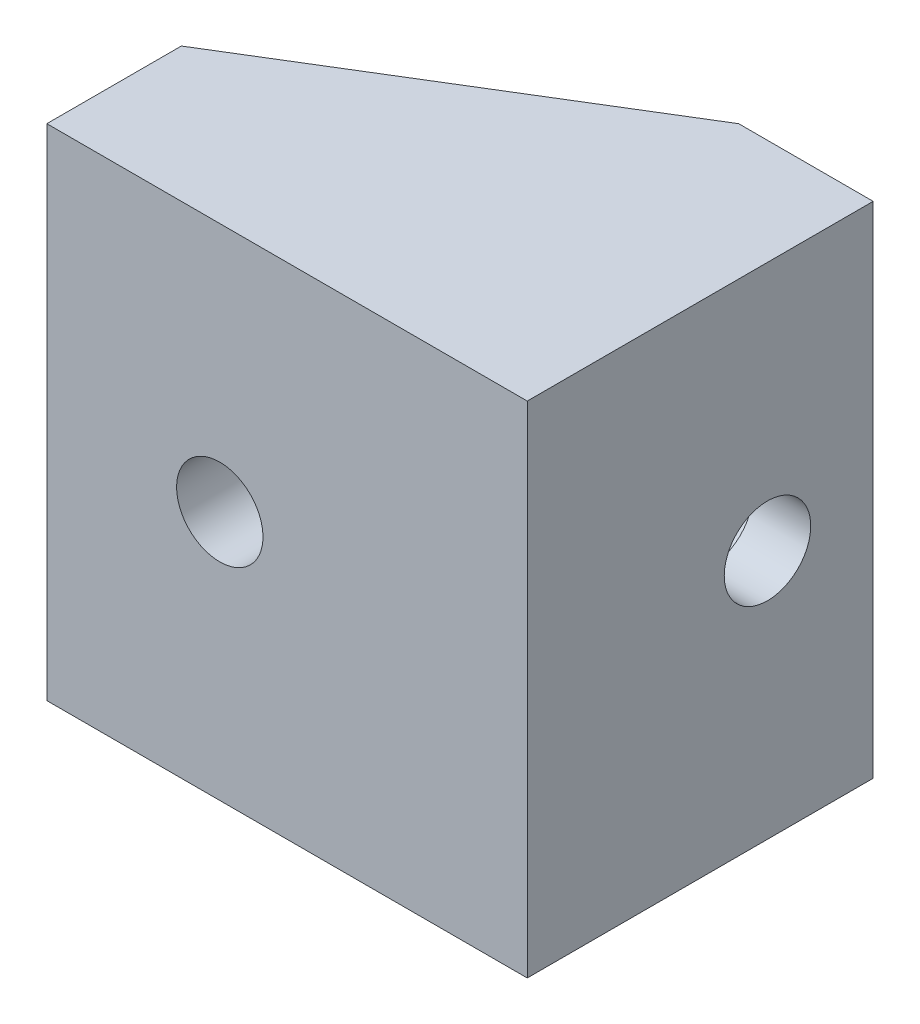
SolidWorks part; units mm, degrees
ref_plane "Front Plane" through (0, 0, 0) normal (0, 0, 1) x (1, 0, 0)
ref_plane "Top Plane" through (0, 0, 0) normal (0, 1, 0) x (1, 0, 0)
ref_plane "Right Plane" through (0, 0, 0) normal (1, 0, 0) x (0, 0, -1)
sketch "Sketch1" plane through (0, 0, 0) normal (0, 1, 0) x (1, 0, 0)
  line L0 (0, 0) -> (0, 11)
  line L1 (0, 11) -> (7, 11)
  line L2 (7, 11) -> (7, -7)
  line L3 (7, -7) -> (-18, -7)
  line L4 (-18, -7) -> (-18, 0)
  line L5 (-18, 0) -> (0, 0)
  dimension "D1" = 11
  dimension "D2" = 7
  dimension "D3" = 18
extrude "Boss-Extrude1" add sketch "Sketch1" along normal blind 20
sketch "Sketch2" plane through (0, 0, 0) normal (-1, 0, 0) x (0, 0, 1)
  line L1 (7, 20) -> (7, 0) construction
  line L2 (-11, 10) -> (0, 10) construction
  line L3 (-11, 20) -> (-11, 0) construction
  line L4 (0, 20) -> (0, 0) construction
  point P4 (-5.5, 10)
  dimension "D1" = 12.5
hole_wizard "CBORE for M4 SHCS1" positions "Sketch2" profile "Sketch3" counterbore size "M4" standard "ANSI Metric" end condition through all
sketch "Sketch3" plane through (0, 10, -5.5) normal (0, 1, 0) x (0, 0, 1)
  line L0 (0, 0) -> (0, 7)
  line L1 (0, 7) -> (2.25, 7)
  line L3 (2.25, 7) -> (2.25, 4)
  line L4 (2.25, 4) -> (4, 4)
  line L5 (4, 4) -> (4, 0)
  line L7 (4, 0) -> (0, 0)
  line L11 (0, -6.35) -> (0, 107.95) construction
  dimension "Thru Hole Dia." = 4.5
  dimension "Thru Hole Depth" = 7
  dimension "C'Bore Dia." = 8
  dimension "C'Bore Depth" = 4
sketch "Sketch4" plane through (0, 0, 0) normal (0, 0, -1) x (-1, 0, 0)
  line L2 (0, 10) -> (18, 10) construction
  line L3 (0, 20) -> (0, 0) construction
  line L4 (18, 20) -> (18, 0) construction
  point P4 (9, 10)
hole_wizard "CSK for #8 Flat Head Socket Cap Screw1" positions "Sketch4" profile "Sketch5" countersink size "#8" standard "ANSI Inch" end condition through all
sketch "Sketch5" plane through (-9, 10, 0) normal (1, 0, 0) x (0, 1, 0)
  line L0 (0, 0) -> (0, 7)
  line L1 (0, 7) -> (2.2479, 7)
  line L2 (2.2479, 7) -> (2.2479, 3.258)
  line L3 (2.2479, 3.258) -> (5.08, 0)
  line L5 (5.08, 0) -> (0, 0)
  line L6 (-2.2479, 3.258) -> (-5.08, 0) construction
  line L11 (0, -6.35) -> (0, 107.95) construction
  dimension "Thru Hole Dia." = 4.4958
  dimension "Thru Hole Depth" = 7
  dimension "Near C'Sink Dia." = 10.16
  dimension "Near C'Sink Angle" = 82
sketch "Sketch6" plane through (0, 0, 0) normal (0, -1, 0) x (1, 0, 0)
  line L0 (-18, 7) -> (7, 7)
  line L1 (7, 7) -> (7, -11)
  line L2 (7, -11) -> (0, -11)
  line L3 (0, -11) -> (-18, 0)
  line L4 (-18, 0) -> (-18, 7)
extrude "Boss-Extrude2" add sketch "Sketch6" along normal blind 3
extrude "Boss-Extrude3" add sketch "Sketch6<2>" against normal blind 3 from surface starting at face at (-3.6667, 20, -1.3333)
sketch "Sketch6<2>" plane through (0, 0, 0) normal (0, -1, 0) x (1, 0, 0) same geometry as "Sketch6"
